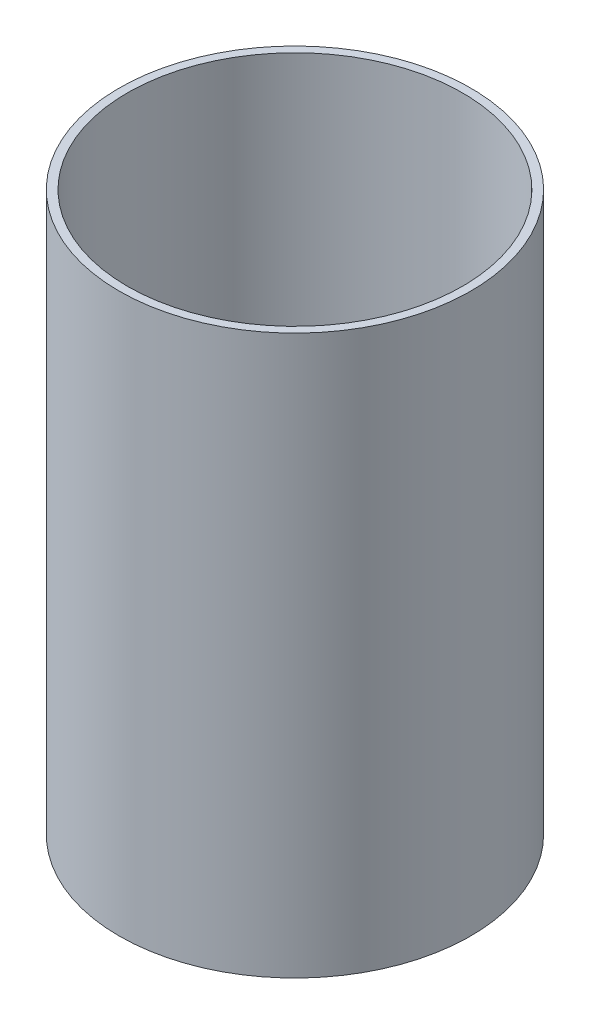
SolidWorks part; units mm, degrees
ref_plane "Front Plane" through (0, 0, 0) normal (0, 0, 1) x (1, 0, 0)
ref_plane "Top Plane" through (0, 0, 0) normal (0, 1, 0) x (1, 0, 0)
ref_plane "Right Plane" through (0, 0, 0) normal (1, 0, 0) x (0, 0, -1)
sketch "Sketch1" plane through (0, 0, 0) normal (0, 1, 0) x (1, 0, 0)
  circle A0 centre (0, 0) radius 81
  circle A1 centre (0, 0) radius 85
  dimension "D1" = 162
  dimension "D2" = 170
extrude "Boss-Extrude1" add sketch "Sketch1" along normal blind 270
